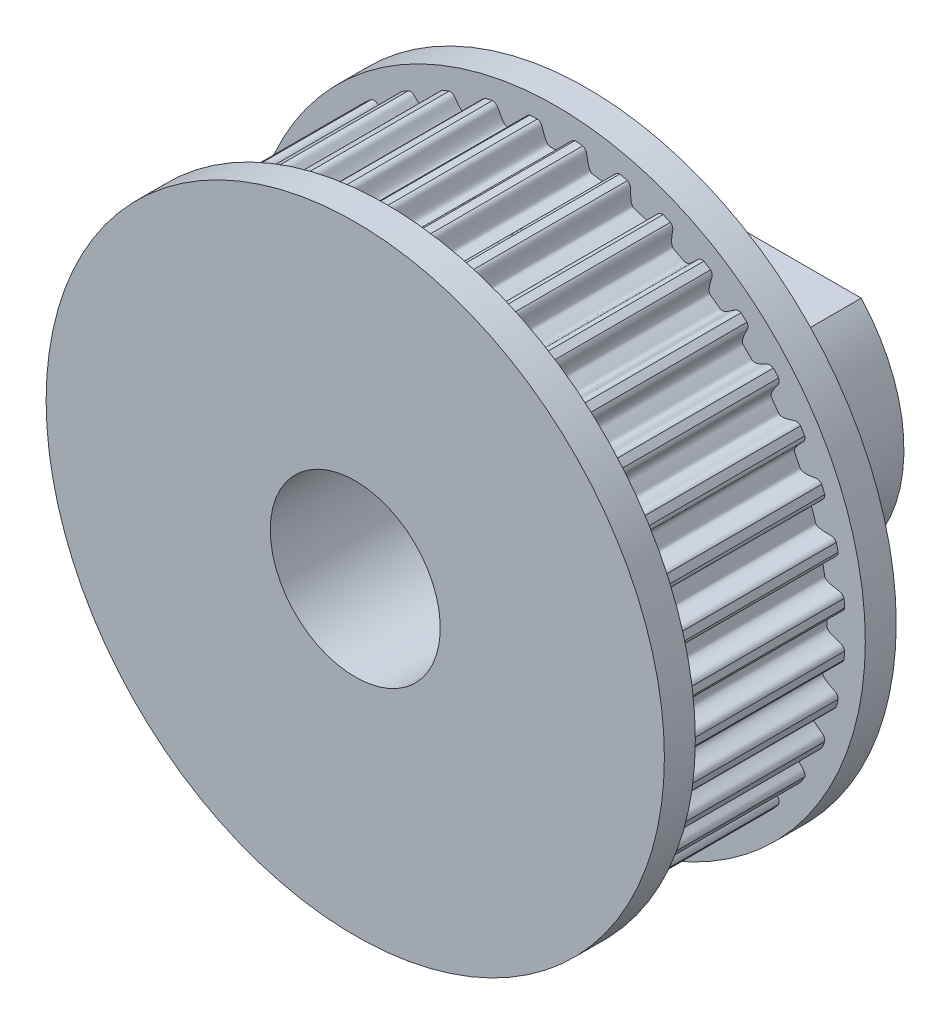
SolidWorks part; units mm, degrees
ref_plane "前视基准面" through (0, 0, 0) normal (0, 0, 1) x (1, 0, 0)
ref_plane "上视基准面" through (0, 0, 0) normal (0, 1, 0) x (1, 0, 0)
ref_plane "右视基准面" through (0, 0, 0) normal (1, 0, 0) x (0, 0, -1)
other "Configuration Table"
ref_axis "基准轴1" through (0, 0, 55) along (0, 0, -1)
sketch "SketchRevolveGearBelt01" plane through (0, 0, 0) normal (1, 0, 0) x (0, 0, -1)
  line L0 (0, 0) -> (1, 0) construction
  line L1 (9.774, 0) -> (9.774, 16.6986)
  line L2 (9.774, 16.6986) -> (9.012, 16.6986)
  line L3 (9.012, 16.6986) -> (9.012, 18.947)
  line L4 (9.012, 18.947) -> (9.48, 20.077)
  line L5 (9.48, 20.077) -> (8.7761, 20.3686)
  line L6 (8.7761, 20.3686) -> (8.25, 19.0986)
  line L7 (8.25, 19.0986) -> (8.25, 18.7036)
  line L8 (8.25, 18.7036) -> (-8.25, 18.7036)
  line L9 (-8.25, 18.7036) -> (-8.25, 19.0986)
  line L10 (-8.25, 19.0986) -> (-8.7761, 20.3686)
  line L11 (-8.7761, 20.3686) -> (-9.48, 20.077)
  line L12 (-9.48, 20.077) -> (-9.012, 18.947)
  line L13 (-9.012, 18.947) -> (-9.012, 16.6986)
  line L14 (-9.012, 16.6986) -> (-9.774, 16.6986)
  line L15 (-9.774, 16.6986) -> (-9.774, 0)
  line L16 (-9.774, 0) -> (9.774, 0)
  dimension "GearBeltFlange1OutsideLength" = 2.2484
  dimension "GearBeltFlange1X" = 0.468
  dimension "GearBeltFlange1Y" = 1.13
  dimension "GearBeltFlangeThickness" = 0.762
  dimension "GearBeltFlangeInside" = 0.395
  dimension "GearBeltOutsideDiameter" = 18.7036
  dimension "GearBeltFlange2X" = 0.468
revolve "Gates_PowerGrip_GT_3mm, 15mm Belt Width" add sketch "SketchRevolveGearBelt01" angle 360 about L0
sketch "SketchToothGearBelt01" plane through (0, 0, 0) normal (0, 0, 1) x (1, 0, 0)
  arc A0 (18.672, 1.2925) -> (18.672, -1.2925) centre (0, 0) cw
  spline S0 degree 3 poles (18.672, -1.2925) (18.6721, -1.2665) (18.6684, -1.2275) (18.6561, -1.177) (18.6432, -1.1401) (18.6267, -1.1047) (18.6069, -1.0711) (18.5839, -1.0396) (18.558, -1.0104) (18.5293, -0.9839) (18.4982, -0.9604) (18.465, -0.94) (18.4299, -0.9227) (18.3713, -0.9019) (18.2964, -0.8793) (18.2078, -0.8512) (18.1291, -0.8247) (18.0552, -0.7983) (17.986, -0.7718) (17.9216, -0.7454) (17.862, -0.7189) (17.8071, -0.6925) (17.757, -0.666) (17.7116, -0.6396) (17.6709, -0.6131) (17.6351, -0.5867) (17.6039, -0.5602) (17.5775, -0.5337) (17.5558, -0.5071) (17.5388, -0.4805) (17.5266, -0.4538) (17.5191, -0.4269) (17.5158, -0.3755) (17.5206, -0.3) (17.5208, -0.2) (17.5219, -0.1) (17.5221, 0) (17.5219, 0.1) (17.5208, 0.2) (17.5206, 0.3) (17.5158, 0.3755) (17.5191, 0.4269) (17.5266, 0.4538) (17.5388, 0.4805) (17.5558, 0.5071) (17.5775, 0.5337) (17.6039, 0.5602) (17.6351, 0.5867) (17.6709, 0.6131) (17.7116, 0.6396) (17.757, 0.666) (17.8071, 0.6925) (17.862, 0.7189) (17.9216, 0.7454) (17.986, 0.7718) (18.0552, 0.7983) (18.1291, 0.8247) (18.2078, 0.8512) (18.2964, 0.8793) (18.3713, 0.9019) (18.4299, 0.9227) (18.465, 0.94) (18.4982, 0.9604) (18.5293, 0.9839) (18.558, 1.0104) (18.5839, 1.0396) (18.6069, 1.0711) (18.6267, 1.1047) (18.6432, 1.1401) (18.6561, 1.177) (18.6684, 1.2275) (18.6721, 1.2665) (18.672, 1.2925) knots 0 0 0 0 0.019856 0.029784 0.039712 0.04964 0.059568 0.069496 0.079424 0.089352 0.09928 0.109208 0.119136 0.129064 0.156684 0.178987 0.200135 0.220136 0.238998 0.256731 0.273348 0.288863 0.303293 0.316663 0.328999 0.340339 0.350727 0.360226 0.368913 0.376892 0.384296 0.39129 0.39807 0.423571 0.449047 0.474524 0.5 0.525476 0.550953 0.576429 0.60193 0.60871 0.615704 0.623108 0.631087 0.639774 0.649273 0.659661 0.671001 0.683337 0.696707 0.711137 0.726652 0.743269 0.761002 0.779864 0.799865 0.821013 0.843316 0.870936 0.880864 0.890792 0.90072 0.910648 0.920576 0.930504 0.940432 0.95036 0.960288 0.970216 0.980144 1 1 1 1
extrude "ToothExtrudeCutGearBelt01" cut sketch "SketchToothGearBelt01" against normal blind 8.25 and the other way blind 8.25
pattern_circular "Tooth Pattern, 40" count 40 every 9 about axis through (0, 0, 55) along (0, 0, -1) of "ToothExtrudeCutGearBelt01"
sketch "BoreRevolveSketch" plane through (0, 0, 0) normal (1, 0, 0) x (0, 0, -1)
  line L0 (0, 0) -> (1, 0) construction
  line L1 (-9.774, 0) -> (9.774, 0)
  line L2 (9.774, 0) -> (9.774, 5)
  line L3 (9.774, 5) -> (-9.774, 5)
  line L4 (-9.774, 5) -> (-9.774, 0)
  dimension "TaperSide1" = 5
  dimension "TaperSide2" = 5
revolve "BoreRevolveCut" cut sketch "BoreRevolveSketch" angle 360 about L0
sketch "AuxiliarySketchGearBelt01" plane through (0, 0, 0) normal (0, 0, 1) x (1, 0, 0)
  circle A0 centre (0, 0) radius 19.0986 construction
  dimension "PitchDiameter" = 38.1972
sketch "草图5" plane through (0, 0, 9.774) normal (0, 0, 1) x (1, 0, 0)
  circle A0 centre (0, 0) radius 25.43
extrude "切除-拉伸2" cut sketch "草图5" against normal blind 4.55
sketch "草图6" plane through (0, 0, -9.774) normal (0, 0, -1) x (-1, 0, 0)
  circle A0 centre (0, 0) radius 21.9936
extrude "切除-拉伸3" cut sketch "草图6" against normal blind 4
sketch "草图7" plane through (0, 0, 5.224) normal (0, 0, 1) x (1, 0, 0)
  circle A0 centre (0, 0) radius 20
  dimension "D1" = 40
extrude "凸台-拉伸1" add sketch "草图7" along normal blind 2
sketch "草图8" plane through (0, 0, -5.774) normal (0, 0, -1) x (-1, 0, 0)
  circle A0 centre (0, 0) radius 20
extrude "凸台-拉伸2" add sketch "草图8" along normal blind 2
sketch "草图9" plane through (0, 0, -7.774) normal (0, 0, -1) x (-1, 0, 0)
  circle A0 centre (0, 0) radius 5.5
  dimension "D1" = 11
extrude "切除-拉伸5" cut sketch "草图9" against normal blind 2
sketch "草图10" plane through (0, 0, -7.774) normal (0, 0, -1) x (-1, 0, 0)
  circle A0 centre (0, 0) radius 5.5
  dimension "D1" = 11
extrude "切除-拉伸6" cut sketch "草图10" against normal through all
sketch "草图11" plane through (0, 0, -7.774) normal (0, 0, -1) x (-1, 0, 0)
  circle A2 centre (0, 0) radius 10.5
  circle A3 centre (0, 0) radius 3.25
  dimension "D1" = 6.5
extrude "凸台-拉伸4" add sketch "草图11" along normal blind 10
sketch "草图13" plane through (0, 0, -17.774) normal (0, 0, -1) x (-1, 0, 0)
  line L0 (0, 0) -> (0, 2.1)
  line L1 (-1000, 2.1) -> (49000, 2.1)
  circle A0 centre (0, 0) radius 3.25
  circle M3 centre (0, 0) radius 3.25
  dimension "D1" = 2.1
extrude "凸台-拉伸5" add sketch "草图13" against normal blind 10 contours L1 M3 region at (0, 2.5678, -17.774)
sketch "草图14" plane through (0, 0, -17.774) normal (0, 0, -1) x (-1, 0, 0)
  line L1 (-1001.7675, 7.1) -> (48998.2325, 7.1)
  line L2 (-2.4804, 7.1) -> (2.4804, 7.1)
  line L3 (-2.4804, 7.1) -> (2.4804, 7.1)
  circle A0 centre (0, 0) radius 10.5
  circle A1 centre (0, 0) radius 10.5
  circle A2 centre (0, 0) radius 10.5
  circle M3 centre (0, 0) radius 10.5
  dimension "D1" = 0
  dimension "D2" = 5
extrude "切除-拉伸7" cut sketch "草图14" against normal blind 10 contours L1 M3 region at (0, 8.4808, -17.774)
sketch "草图15" plane through (0, 7.1, 0) normal (0, 1, 0) x (1, 0, 0)
  line L0 (0, -55) -> (0, 55) construction
  line L1 (7.7356, 17.774) -> (-7.7356, 17.774) construction
  circle A0 centre (0, 12.774) radius 1.6
  dimension "D1" = 3.2
  dimension "D2" = 5
extrude "切除-拉伸9" cut sketch "草图15" against normal up to next
fillet "圆角2" radius 2 2 edges at (0, 7.1, -7.774) (0, -10.5, -7.774)
